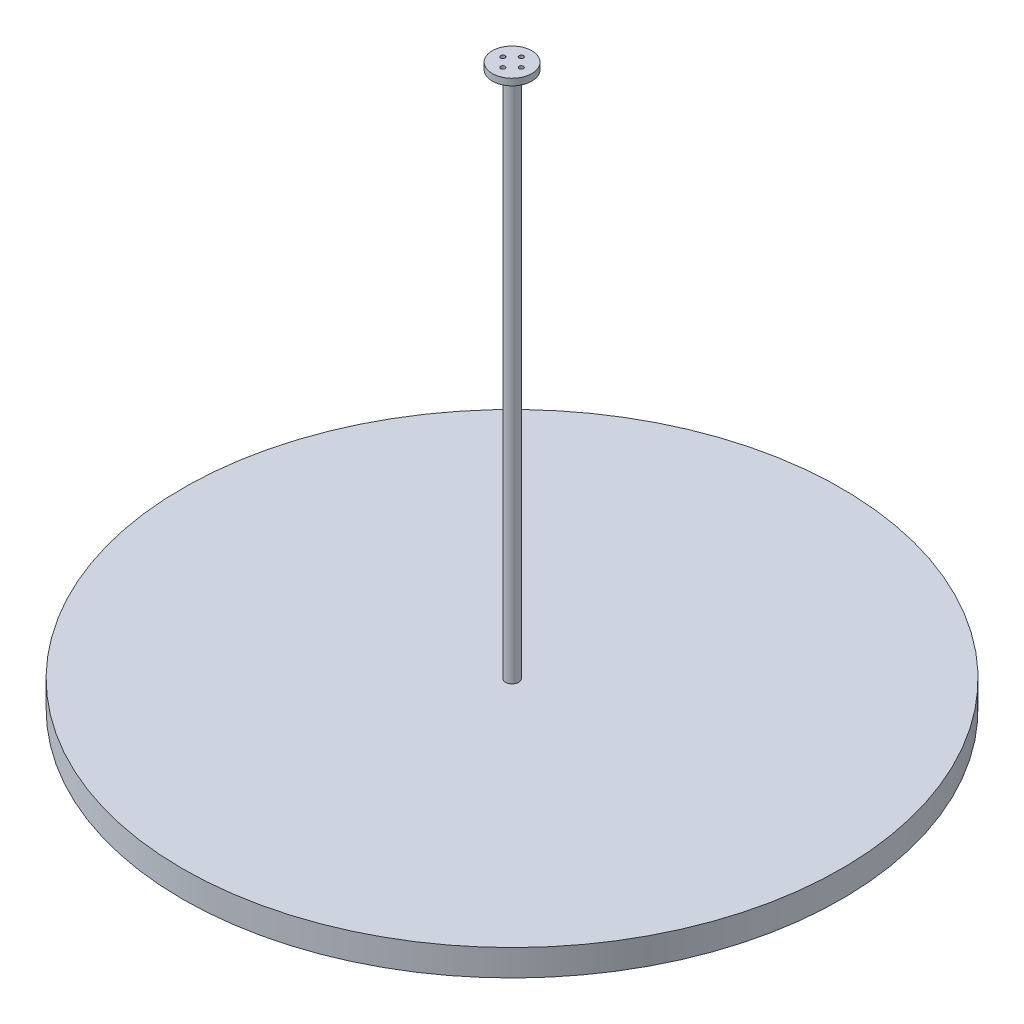
SolidWorks part; units mm, degrees
ref_plane "前视基准面" through (0, 0, 0) normal (0, 0, 1) x (1, 0, 0)
ref_plane "上视基准面" through (0, 0, 0) normal (0, 1, 0) x (1, 0, 0)
ref_plane "右视基准面" through (0, 0, 0) normal (1, 0, 0) x (0, 0, -1)
sketch "草图1" plane through (0, 0, 0) normal (0, 1, 0) x (1, 0, 0)
  circle A0 centre (0, 0) radius 250
  dimension "D1" = 500
extrude "凸台-拉伸1" add sketch "草图1" along normal blind 20
sketch "草图2" plane through (0, 20, 0) normal (0, 1, 0) x (1, 0, 0)
  circle A0 centre (0, 0) radius 5
  dimension "D1" = 10
extrude "凸台-拉伸2" add sketch "草图2" along normal blind 400
sketch "草图3" plane through (0, 420, 0) normal (0, 1, 0) x (1, 0, 0)
  circle A0 centre (0, 0) radius 15
  dimension "D1" = 30
extrude "凸台-拉伸3" add sketch "草图3" along normal blind 5
sketch "草图4" plane through (0, 425, 0) normal (0, 1, 0) x (1, 0, 0)
  line L0 (-15, 0) -> (15, 0) construction
  circle A0 centre (0, 0) radius 15 construction
  circle A1 centre (-7, 0) radius 1.65
  dimension "D1" = 3.3
  dimension "D2" = 7
extrude "切除-拉伸1" cut sketch "草图4" against normal blind 5
pattern_circular "阵列(圆周)1" count 4 over 360 about axis through (0, 425, 0) along (0, -1, 0) of "切除-拉伸1"
